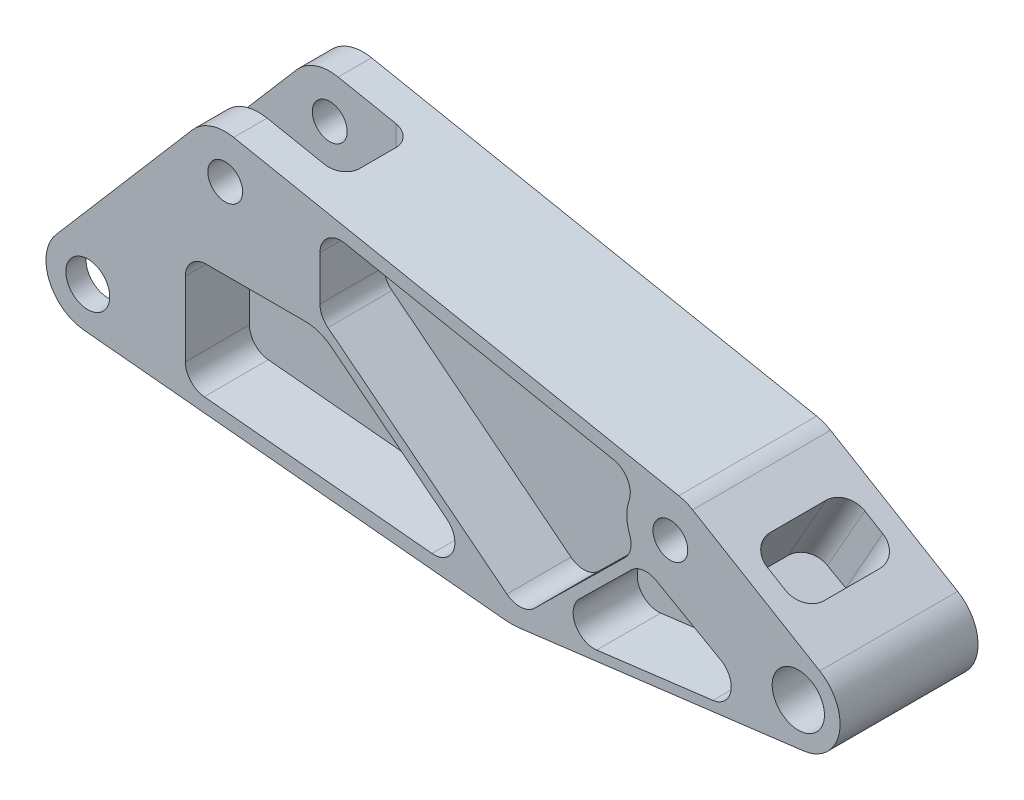
SolidWorks part; units mm, degrees
material "6061-T6 (SS)"
ref_plane "Front Plane" through (0, 0, 0) normal (1, 0, 0) x (0, 1, 0)
ref_plane "Top Plane" through (0, 0, 0) normal (0, 0, 1) x (0, 1, 0)
ref_plane "Right Plane" through (0, 0, 0) normal (0, 1, 0) x (-1, 0, 0)
sketch "Sketch1" plane through (0, 0, 0) normal (0, 0, 1) x (0, 1, 0)
  line L1 (21.356, 21.793) -> (37.358, 102.9455)
  line L2 (5.8317, 135.319) -> (34.7405, 110.5039)
  line L3 (6.5414, -3.9083) -> (20.3824, 19.2574)
  line L5 (14.8385, 114.2971) -> (14.8385, 127.5877)
  line L6 (16.8705, 89.241) -> (16.8705, 125.8434)
  line L9 (-2.4791, 111.7571) -> (11.0285, 111.7571)
  line L10 (16.8705, 89.241) -> (34.6557, 89.241)
  line L12 (4.2983, 19.4547) -> (-1.3308, 9.5091)
  line L14 (14.8385, 107.9471) -> (14.8385, 89.9006)
  line L15 (-13.1015, 50.4298) -> (20.0455, 92.416) construction
  line L16 (-6.2716, 108.311) -> (-10.2563, 66.785)
  line L17 (-14.2126, 52.1469) -> (-6.7167, 130.2649)
  line L20 (13.1993, 85.1789) -> (-3.4733, 64.0603)
  line L21 (15.9233, 85.7599) -> (-9.8354, 53.1323)
  line L23 (30.7695, 82.662) -> (21.1158, 33.7042)
  line L25 (18.9137, 87.209) -> (27.0315, 87.209)
  line L26 (4.2983, 19.4547) -> (16.4059, 12.6019)
  line L27 (-1.3308, 9.5091) -> (10.5427, 2.7888)
  line L28 (-13.1015, 50.4298) -> (13.5685, 23.3286) construction
  line L29 (-10.4937, 36.7653) -> (-7.8375, 15.5634)
  line L30 (-9.5606, 48.0991) -> (6.6502, 31.6262)
  line L31 (-0.7413, 14.1604) -> (5.9072, 25.9071)
  line L32 (14.8385, 114.2971) -> (-8.2489, 114.2971)
  line L33 (5.3071, 30.4561) -> (-3.9976, 39.9113)
  line L34 (-7.5609, -0.9472) -> (-14.2126, 52.1469)
  circle A0 centre (0, 0) radius 4.7625
  circle A1 centre (29.5705, 104.481) radius 3.175
  circle A2 centre (0.8685, 129.5371) radius 4
  circle A3 centre (13.5685, 23.3286) radius 3.175
  arc A4 (-7.5609, -0.9472) -> (6.5414, -3.9083) centre (0, 0) ccw
  arc A5 (-6.7167, 130.2649) -> (5.8317, 135.319) centre (0.8685, 129.5371) cw
  arc A6 (37.358, 102.9455) -> (34.7405, 110.5039) centre (29.5705, 104.481) ccw
  arc A7 (20.3824, 19.2574) -> (21.356, 21.793) centre (13.5685, 23.3286) ccw
  arc A17 (21.1158, 33.7042) -> (16.1423, 30.8372) centre (17.3778, 34.4413) cw
  arc A23 (14.8385, 89.9006) -> (13.1993, 85.1789) centre (7.2185, 89.9006) cw
  arc A24 (-10.2563, 66.785) -> (-3.4733, 64.0603) centre (-6.4637, 66.4211) ccw
  arc A25 (27.0315, 87.209) -> (30.7695, 82.662) centre (27.0315, 83.399) cw
  arc A26 (18.9137, 87.209) -> (15.9233, 85.7599) centre (18.9137, 83.399) ccw
  arc A28 (-2.4791, 111.7571) -> (-6.2716, 108.311) centre (-2.4791, 107.9471) ccw
  arc A29 (-9.8354, 53.1323) -> (-9.5606, 48.0991) centre (-6.845, 50.7714) ccw
  arc A30 (-10.4937, 36.7653) -> (-3.9976, 39.9113) centre (-6.7132, 37.2389) cw
  arc A32 (6.6502, 31.6262) -> (10.7288, 30.7407) centre (9.3658, 34.2986) ccw
  arc A33 (-7.8375, 15.5634) -> (-0.7413, 14.1604) centre (-4.057, 16.037) ccw
  arc A34 (11.0285, 111.7571) -> (14.8385, 107.9471) centre (11.0285, 107.9471) cw
  circle A35 centre (20.0455, 92.416) radius 3.175 construction
  arc A36 (10.7288, 30.7407) -> (16.1423, 30.8372) centre (13.5685, 23.3286) cw
  arc A37 (5.3071, 30.4561) -> (5.9072, 25.9071) centre (2.5915, 27.7837) cw
  dimension "D1" = 38.1
  dimension "D4" = 6.35
  dimension "D5" = 9.525
  dimension "D6" = 8
  dimension "D7" = 26.9875
  dimension "D8" = 7.62
  dimension "D9" = 7.62
  dimension "D10" = 7.9375
  dimension "D11" = 7.9375
  dimension "D19" = 2.54
  dimension "D22" = 1.778
  dimension "D24" = 3.81
  dimension "D25" = 3.81
  dimension "D26" = 1.778
  dimension "D29" = 3.81
  dimension "D30" = 12.7
  dimension "D31" = 3.81
  dimension "D32" = 3.81
  dimension "D33" = 7.62
  dimension "D34" = 3.81
  dimension "D35" = 3.81
  dimension "D36" = 1.27
  dimension "D14" = 3.81
  dimension "D20" = 3.81
  dimension "D28" = 3.81
  dimension "D39" = 6.35
  dimension "D40" = 1.778
  dimension "D12" = 3.81
  dimension "D2" = 129.54
  dimension "D3" = 108.585
  dimension "D13" = 15.24
  dimension "D15" = 13.97
  dimension "D16" = 12.7
  dimension "D17" = 2.032
  dimension "D18" = 2.032
  dimension "D21" = 1.778
  dimension "D23" = 2.54
  dimension "D27" = 2.54
  dimension "D37" = 0.889
  dimension "D38" = 15.24
  dimension "D41" = 13.97
extrude "Boss-Extrude1" add sketch "Sketch1" along normal mid plane 25.146 contours L1 A6 L2 L6 L10 A1 | L3 A7 L1 L10 L6 L2 L5 A4 L27 L12 L26 A28 A23 L20 A24 L16 A17 A3 A0 L23 L21 A26 L25 A25 | A5 L5 L2 A2 | L12 L27 L3 L26 region at (-20.9986, 19.6363, 0) region at (-103.8939, 25.4238, 0) region at (-11.1047, 7.4884, 0) region at (-123.5763, 3.4351, 0)
extrude "Boss-Extrude2" add sketch "Sketch1<5>" along normal mid plane 1.778 contours L16 A24 L20 A23 | A17 | L23 A25 L25 A26 L21 | L29 A33 L31 L33 A30 region at (-90.503, 1.8814, 0) region at (-57.96, 12.4468, 0) region at (-26.9438, -3.1281, 0)
sketch "Sketch1<5>" plane through (0, 0, 0) normal (0, 0, 1) x (0, 1, 0) same geometry as "Sketch1"
extrude "Cut-Extrude1" cut sketch "Sketch1<6>" against normal mid plane 12.954 contours L1 A6 L2 L6 L10 A1 region at (-103.8939, 25.4238, 0)
sketch "Sketch1<6>" plane through (0, 0, 0) normal (0, 0, 1) x (0, 1, 0) same geometry as "Sketch1"
extrude "Cut-Extrude2" cut sketch "Sketch1<7>" against normal mid plane 17.78 contours A5 L5 L2 A2 region at (-123.5763, 3.4351, 0)
sketch "Sketch1<7>" plane through (0, 0, 0) normal (0, 0, 1) x (0, 1, 0) same geometry as "Sketch1"
extrude "Cut-Extrude3" cut sketch "Sketch1<9>" against normal mid plane 17.78 contours L12 L27 L3 L26 region at (-11.1047, 7.4884, 0)
sketch "Sketch1<9>" plane through (0, 0, 0) normal (0, 0, 1) x (0, 1, 0) same geometry as "Sketch1"
fillet "Fillet1" radius 3.81 8 edges at (-120.9424, 14.8385, 8.89) (-120.9424, 14.8385, -8.89) (-107.5422, 16.8705, 6.477) (-107.5422, 16.8705, -6.477) (-6.1489, 4.606, -8.89) (-16.0283, 10.3521, -8.89) (-16.0283, 10.3521, 8.89) (-6.1489, 4.606, 8.89)
fillet "Fillet2" radius 3.175 10 edges at (-89.241, 27.6681, -6.477) (-89.241, 17.9864, -5.3611) (-89.241, 27.6681, 6.477) (-89.241, 17.9864, 5.3611) (-89.241, 16.8705, 0) (-114.2971, 1.3898, -8.89) (-114.2971, 13.7226, -7.7741) (-114.2971, 1.3898, 8.89) (-114.2971, 13.7226, 7.7741) (-114.2971, 14.8385, 0)
sketch "Sketch2" plane through (0, 0, 0) normal (0, 0, 1) x (0, 1, 0)
  line L0 (0.8685, 129.5371) -> (-82.2041, 143.266)
  line L1 (29.5705, 104.481) -> (77.0079, 96.6413)
  line L2 (0.8685, 129.5371) -> (0, 0) construction
  dimension "D1" = 99
fillet "Fillet3" radius 12.7 1 edges at (-52.1469, -14.2126, 0)
